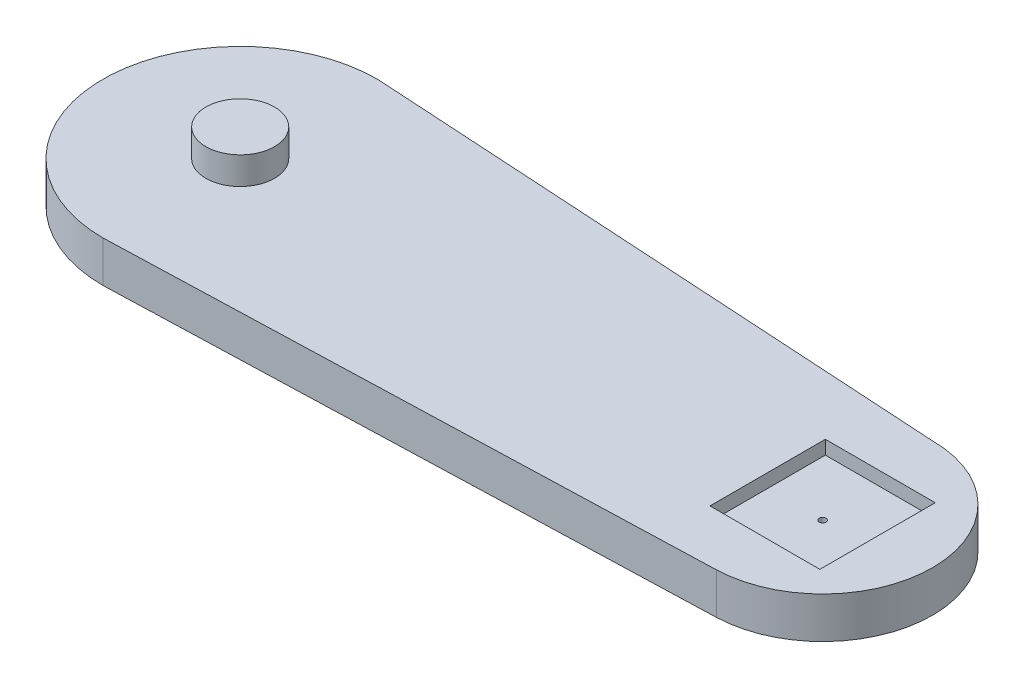
SolidWorks part; units mm, degrees
ref_plane "Alzado" through (0, 0, 0) normal (0, 0, 1) x (1, 0, 0)
ref_plane "Planta" through (0, 0, 0) normal (0, 1, 0) x (1, 0, 0)
ref_plane "Vista lateral" through (0, 0, 0) normal (1, 0, 0) x (0, 0, -1)
sketch "Croquis1" plane through (0, 0, 0) normal (0, 1, 0) x (1, 0, 0)
  line L0 (0, 0) -> (215, -2.9978) construction
  line L1 (0, 50) -> (215, 37.0022)
  line L2 (0, -50) -> (216.2981, -42.9767)
  arc A0 (0, 50) -> (0, -50) centre (0, 0) ccw
  arc A1 (216.2981, -42.9767) -> (215, 37.0022) centre (215, -2.9978) ccw
  circle A2 centre (0, 0) radius 1.25
  circle A3 centre (215, -2.9978) radius 1.25
  dimension "D1" = 100
  dimension "D3" = 80
  dimension "D4" = 2.5
  dimension "D5" = 2.5
  dimension "D2" = 215
extrude "Saliente-Extruir1" add sketch "Croquis1" along normal blind 15
sketch "Croquis2" plane through (0, 15, 0) normal (0, 1, 0) x (1, 0, 0)
  circle A0 centre (0, 0) radius 12.5
  dimension "D1" = 25
extrude "Saliente-Extruir2" add sketch "Croquis2" along normal blind 10
sketch "Croquis3" plane through (0, 0, 0) normal (0, -1, 0) x (-1, 0, 0)
  circle A0 centre (0, 0) radius 11
  dimension "D1" = 22
extrude "Cortar-Extruir1" cut sketch "Croquis3" against normal blind 5
sketch "Croquis4" plane through (0, 15, 0) normal (0, 1, 0) x (1, 0, 0)
  line L1 (195, -23.9978) -> (235, -23.9978)
  line L2 (195, -23.9978) -> (195, 18.0022)
  line L3 (195, 18.0022) -> (235, 18.0022)
  line L4 (235, -23.9978) -> (235, 18.0022)
  line L5 (195, -23.9978) -> (235, 18.0022) construction
  line L6 (195, 18.0022) -> (235, -23.9978) construction
  point P0 (215, -2.9978)
  dimension "D1" = 42
  dimension "D2" = 40
extrude "Cortar-Extruir2" cut sketch "Croquis4" against normal blind 5
ref_plane "Plano1" through (-0.0005, 0, 0.0324) normal (-0.014, 0, 0.9999) x (0.9999, 0, 0.014)
